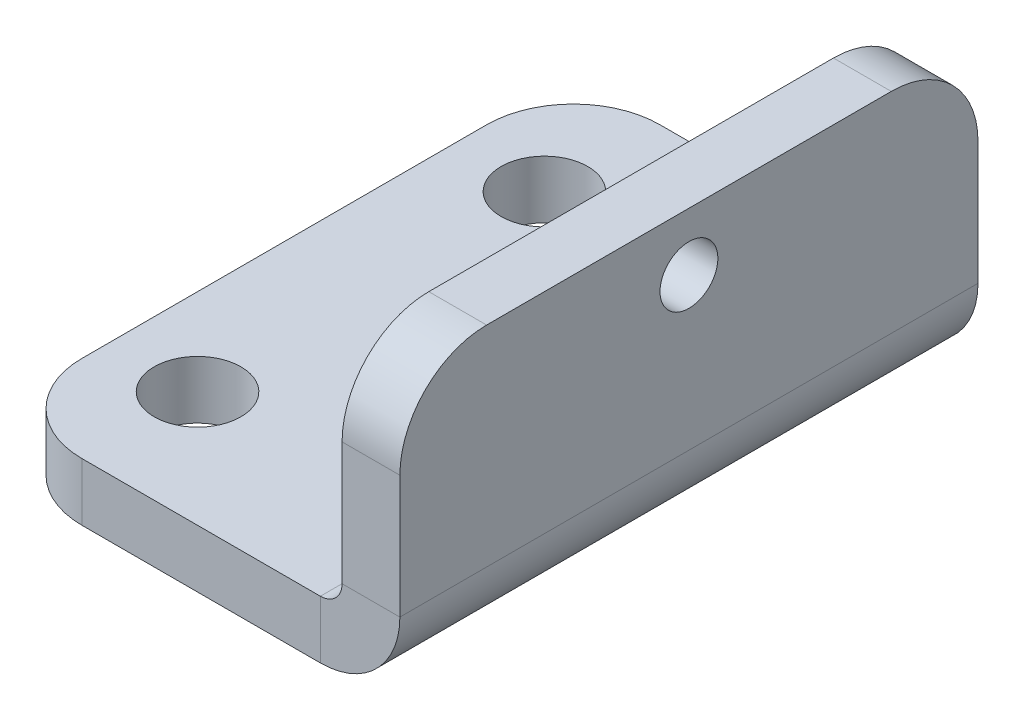
SolidWorks part; units mm, degrees
note: The reader was unsure of these and kept them because the rebuilt part matched: bend radius of "BaseBend1".
ref_plane "Front Plane" through (0, 0, 0) normal (0, 0, 1) x (1, 0, 0)
ref_plane "Top Plane" through (0, 0, 0) normal (0, 1, 0) x (1, 0, 0)
ref_plane "Right Plane" through (0, 0, 0) normal (1, 0, 0) x (0, 0, -1)
sketch "Sketch2" plane through (0, 0, 0) normal (0, 0, 1) x (1, 0, 0)
  line L0 (-12, 0) -> (0, 0)
  line L1 (0, 0) -> (0, 8)
  dimension "D1" = 12
  dimension "D2" = 8
base flange "Base-Flange1" sketch "Sketch2" end condition mid plane depth 20 reverse direction no thickness 2 reverse thickness direction no bend radius 0.75
bend "BaseBend1" bend radius 0.75 bend angle 90 parameters "D5"=1
fillet "Fillet1" radius 3 4 edges at (1, 8, -10) (-12, -1, -10) (1, 8, 10) (-12, -1, 10)
sketch "Sketch8" plane through (0, 0, 0) normal (0, 1, 0) x (1, 0, 0)
  line L0 (-12, -7) -> (-12, 7) construction
  line L1 (0, 0) -> (-12, 0) construction
  circle A0 centre (-9, 6) radius 1.5
  circle A1 centre (-9, -6) radius 1.5
  dimension "D2" = 3
  dimension "D1" = 3
  dimension "D3" = 6
extrude "Cut-Extrude1" cut sketch "Sketch8" against normal through all
sketch "Sketch9" plane through (0, 0, 0) normal (-1, 0, 0) x (0, 0, 1)
  line L0 (7, 8) -> (-7, 8) construction
  circle A0 centre (0, 6) radius 1
  dimension "D1" = 2
  dimension "D2" = 2
extrude "Cut-Extrude2" cut sketch "Sketch9" against normal through all
sketch "Bend-Lines1" [suppressed] plane through (0, 0, 0) normal (0, 1, 0) x (1, 0, 0)
sketch "Bounding-Box1" [suppressed] plane through (0, 0, 0) normal (0, 1, 0) x (1, 0, 0)
sheet metal parameters "Sheet-Metal1" thickness 2 parameters "D1"=0.75
flat pattern "Flat-Pattern1" [suppressed]
sketch "Bend-Lines2" plane through (0, 0, 0) normal (0, 1, 0) x (1, 0, 0)
  line L0 (0.6244, 10) -> (0.6244, -10) construction
  line L1 (0.6244, 10) -> (0.6244, -10) construction
sketch3d "Bounding-Box2" [suppressed]
  line L0 (0, 0, 0) -> (21.2489, 0, 0) construction
  line L1 (0, 20, 0) -> (21.2489, 20, 0) construction
  line L2 (0, 0, 0) -> (0, 20, 0) construction
  line L3 (21.2489, 0, 0) -> (21.2489, 20, 0) construction
bend of the flat pattern "Flatten-<BaseBend1>1"
sheet metal parameters "Sheet-Metal2" thickness 2 parameters "D1"=0.75
flat pattern "Flat-Pattern1"
sketch "Bend-Lines2" plane through (0, 0, 0) normal (0, 1, 0) x (1, 0, 0)
  line L0 (0.6244, 10) -> (0.6244, -10) construction
  line L1 (0.6244, 10) -> (0.6244, -10) construction
sketch3d "Bounding-Box2" [suppressed]
  line L0 (0, 0, 0) -> (21.2489, 0, 0) construction
  line L1 (0, 20, 0) -> (21.2489, 20, 0) construction
  line L2 (0, 0, 0) -> (0, 20, 0) construction
  line L3 (21.2489, 0, 0) -> (21.2489, 20, 0) construction
bend of the flat pattern "Flatten-<BaseBend1>1"
sheet metal parameters "Sheet-Metal3" thickness 2 parameters "D1"=0.75
flat pattern "Flat-Pattern1"
sketch "Bend-Lines2" plane through (0, 0, 0) normal (0, 1, 0) x (1, 0, 0)
  line L0 (0.6244, 10) -> (0.6244, -10) construction
  line L1 (0.6244, 10) -> (0.6244, -10) construction
sketch3d "Bounding-Box2" [suppressed]
  line L0 (0, 0, 0) -> (21.2489, 0, 0) construction
  line L1 (0, 20, 0) -> (21.2489, 20, 0) construction
  line L2 (0, 0, 0) -> (0, 20, 0) construction
  line L3 (21.2489, 0, 0) -> (21.2489, 20, 0) construction
bend of the flat pattern "Flatten-<BaseBend1>1"
